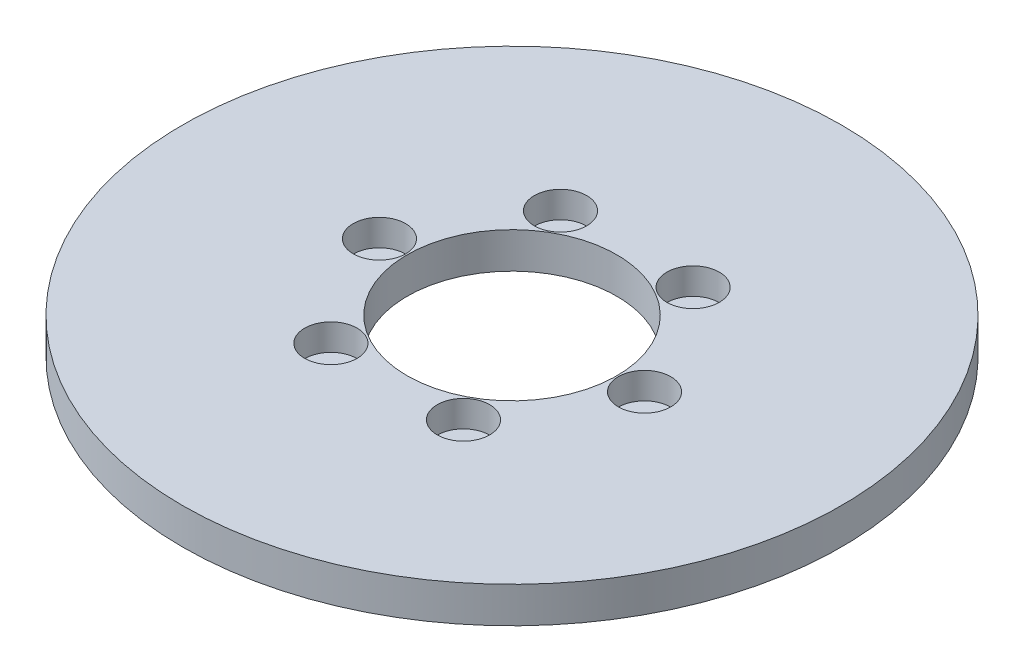
SolidWorks part; units mm, degrees
ref_plane "Front Plane" through (0, 0, 0) normal (0, 0, 1) x (1, 0, 0)
ref_plane "Top Plane" through (0, 0, 0) normal (0, 1, 0) x (1, 0, 0)
ref_plane "Right Plane" through (0, 0, 0) normal (1, 0, 0) x (0, 0, -1)
sketch "Sketch1" plane through (0, 0, 0) normal (0, 1, 0) x (1, 0, 0)
  circle A0 centre (0, 0) radius 55
  dimension "FLANGE_OD" = 110
extrude "Boss-Extrude1" add sketch "Sketch1" along normal blind 6
sketch "Sketch2" plane through (0, 0, 0) normal (0, 1, 0) x (1, 0, 0)
  circle A0 centre (0, 0) radius 17.5
  dimension "BORE_D" = 35
extrude "Cut-Extrude1" cut sketch "Sketch2" along normal through all
sketch "Sketch3" plane through (0, 6, 0) normal (0, 1, 0) x (1, 0, 0)
  circle A0 centre (0, 0) radius 22.1228 construction
  circle A1 centre (-22.1228, 0) radius 4.3763
  dimension "BOLT_D" = 8.7526
  dimension "BOLT_PCD" = 44.2456
extrude "Cut-Extrude2" cut sketch "Sketch3" against normal blind 4.4091
pattern_circular "CirPattern1" count 6 over 360 about axis through (0, 0, 0) along (0, 1, 0) of "Cut-Extrude2"
